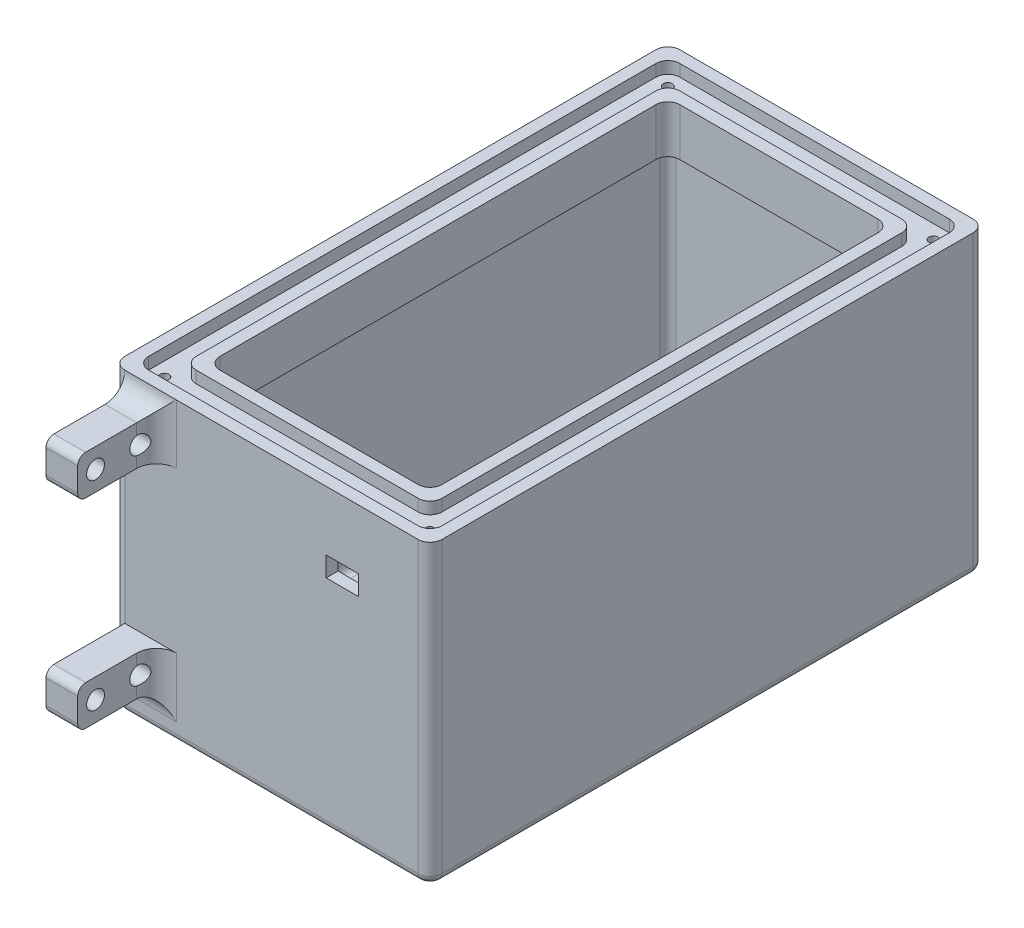
SolidWorks part; units mm, degrees
material "ABS"
ref_plane "Front Plane" through (0, 0, 0) normal (0, 0, 1) x (1, 0, 0)
ref_plane "Top Plane" through (0, 0, 0) normal (0, 1, 0) x (1, 0, 0)
ref_plane "Right Plane" through (0, 0, 0) normal (1, 0, 0) x (0, 0, -1)
sketch "Sketch1" plane through (0, 0, 0) normal (0, 1, 0) x (1, 0, 0)
  line L1 (0, 0) -> (80, 0)
  line L2 (0, 0) -> (0, 140)
  line L3 (0, 140) -> (80, 140)
  line L4 (80, 0) -> (80, 140)
  dimension "D1" = 140
  dimension "D2" = 80
extrude "Boss-Extrude1" add sketch "Sketch1" along normal blind 3
sketch "Sketch2" plane through (0, 3, 0) normal (0, 1, 0) x (1, 0, 0)
  line L1 (0, 140) -> (80, 140)
  line L2 (0, 140) -> (0, 0)
  line L3 (0, 0) -> (80, 0)
  line L4 (80, 140) -> (80, 0)
  line L5 (3, 137) -> (77, 137)
  line L6 (3, 137) -> (3, 3)
  line L7 (3, 3) -> (77, 3)
  line L8 (77, 137) -> (77, 3)
  dimension "D1" = 3
  dimension "D2" = 3
  dimension "D3" = 3
  dimension "D4" = 3
extrude "Boss-Extrude2" add sketch "Sketch2" along normal blind 60
fillet "Fillet1" radius 2 8 edges at (40, 3, -3) (77, 3, -70) (3, 3, -70) (40, 3, -137) (77, 33, -3) (3, 33, -3) (77, 33, -137) (3, 33, -137)
fillet "Fillet2" radius 2 4 edges at (40, 0, -140) (0, 0, -70) (40, 0, 0) (80, 0, -70)
sketch "Sketch6" plane through (0, 63, 0) normal (0, 1, 0) x (1, 0, 0)
  line L1 (0, 140) -> (80, 140)
  line L2 (0, 140) -> (0, 0)
  line L3 (0, 0) -> (80, 0)
  line L4 (80, 140) -> (80, 0)
  line L5 (15, 128) -> (65, 128)
  line L6 (12, 125) -> (12, 15)
  line L7 (15, 12) -> (65, 12)
  line L8 (68, 125) -> (68, 15)
  arc A0 (65, 12) -> (68, 15) centre (65, 15) ccw
  arc A1 (12, 15) -> (15, 12) centre (15, 15) ccw
  arc A2 (65, 128) -> (68, 125) centre (65, 125) cw
  arc A3 (15, 128) -> (12, 125) centre (15, 125) ccw
  dimension "D5" = 3
  dimension "D1" = 12
  dimension "D2" = 12
  dimension "D3" = 12
  dimension "D4" = 12
extrude "Boss-Extrude3" add sketch "Sketch6" along normal blind 12
sketch "Sketch7" plane through (0, 75, 0) normal (0, 1, 0) x (1, 0, 0)
  line L0 (80, 140) -> (0, 140) construction
  line L1 (6, 137) -> (74, 137)
  line L2 (3, 134) -> (3, 6)
  line L3 (6, 3) -> (74, 3)
  line L4 (77, 134) -> (77, 6)
  line L5 (80, 0) -> (80, 140) construction
  line L6 (0, 0) -> (80, 0) construction
  line L7 (0, 140) -> (0, 0) construction
  line L13 (12, 131) -> (68, 131)
  line L14 (9, 128) -> (9, 12)
  line L15 (12, 9) -> (68, 9)
  line L16 (71, 128) -> (71, 12)
  arc A0 (3, 6) -> (6, 3) centre (6, 6) ccw
  arc A1 (74, 3) -> (77, 6) centre (74, 6) ccw
  arc A2 (74, 137) -> (77, 134) centre (74, 134) cw
  arc A3 (6, 137) -> (3, 134) centre (6, 134) ccw
  arc A7 (9, 12) -> (12, 9) centre (12, 12) ccw
  arc A8 (68, 9) -> (71, 12) centre (68, 12) ccw
  arc A9 (68, 131) -> (71, 128) centre (68, 128) cw
  arc A10 (12, 131) -> (9, 128) centre (12, 128) ccw
  dimension "D5" = 3
  dimension "D6" = 6
  dimension "D10" = 3
  dimension "D1" = 3
  dimension "D2" = 3
  dimension "D3" = 3
  dimension "D4" = 3
  dimension "D7" = 6
  dimension "D8" = 6
  dimension "D9" = 6
extrude "Cut-Extrude1" cut sketch "Sketch7" against normal blind 3
sketch "Sketch8" plane through (0, 72, 0) normal (0, 1, 0) x (1, 0, 0)
  line L0 (0, 0) -> (80, 0) construction
  line L1 (0, 140) -> (0, 0) construction
  line L2 (80, 0) -> (80, 140) construction
  line L3 (80, 140) -> (0, 140) construction
  circle A0 centre (6.5, 6.5) radius 1.15
  circle A1 centre (73.5, 6.5) radius 1.15
  circle A2 centre (73.5, 133.5) radius 1.15
  circle A3 centre (6.5, 133.5) radius 1.15
  dimension "D1" = 2.3
  dimension "D2" = 2.3
  dimension "D3" = 2.3
  dimension "D4" = 2.3
  dimension "D5" = 6.5
  dimension "D6" = 6.5
  dimension "D7" = 6.5
  dimension "D8" = 6.5
  dimension "D9" = 6.5
  dimension "D10" = 6.5
  dimension "D11" = 6.5
  dimension "D12" = 6.5
extrude "Cut-Extrude2" cut sketch "Sketch8" against normal blind 6
fillet "Fillet3" radius 3 8 edges at (0.5858, 0.5858, -139.4142) (79.4142, 0.5858, -139.4142) (79.4142, 0.5858, -0.5858) (0.5858, 0.5858, -0.5858) (0, 38.5, -140) (80, 38.5, -140) (80, 38.5, 0) (0, 38.5, 0)
sketch "Sketch9" plane through (0, 0, 0) normal (-1, 0, 0) x (0, 0, 1)
  line L0 (-137, 75) -> (-3, 75) construction
  line L1 (-87, 55) -> (-82, 55)
  line L2 (-87, 55) -> (-87, 29)
  line L3 (-87, 29) -> (-82, 29)
  line L4 (-82, 55) -> (-82, 29)
  line L6 (-140, 2) -> (-140, 75) construction
  line L7 (0, 75) -> (0, 2) construction
  dimension "D1" = 26
  dimension "D2" = 5
  dimension "D3" = 20
  dimension "D4" = 53
  dimension "D5" = 82
extrude "Boss-Extrude4" add sketch "Sketch9" along normal blind 15
sketch "Sketch10" plane through (0, 0, -87) normal (0, 0, -1) x (-1, 0, 0)
  line L0 (15, 29) -> (0, 29) construction
  line L1 (15, 55) -> (10, 55)
  line L2 (15, 55) -> (15, 29)
  line L3 (15, 29) -> (10, 29)
  line L4 (10, 55) -> (10, 29)
  dimension "D1" = 5
extrude "Boss-Extrude5" add sketch "Sketch10" along normal blind 53
fillet "Fillet4" radius 3 4 edges at (0, 29, -84.5) (0, 55, -84.5) (0, 42, -87) (0, 42, -82)
fillet "Fillet5" radius 3 4 edges at (-12.5, 29, -140) (-12.5, 55, -140) (-10, 42, -87) (-15, 42, -82)
sketch "Sketch12" plane through (0, 0, 0) normal (0, 0, 1) x (1, 0, 0)
  line L0 (0, 2) -> (0, 75) construction
  line L1 (3, 70) -> (11, 70)
  line L2 (3, 70) -> (3, 60)
  line L3 (3, 60) -> (11, 60)
  line L4 (11, 70) -> (11, 60)
  line L5 (3, 19.67) -> (11, 19.67)
  line L6 (3, 19.67) -> (3, 9.67)
  line L7 (3, 9.67) -> (11, 9.67)
  line L8 (11, 19.67) -> (11, 9.67)
  line L9 (3, 75) -> (77, 75) construction
  dimension "D1" = 8
  dimension "D2" = 10
  dimension "D3" = 8
  dimension "D4" = 10
  dimension "D5" = 40.33
  dimension "D6" = 3
  dimension "D7" = 5
extrude "Boss-Extrude6" add sketch "Sketch12" along normal blind 19.88
fillet "Fillet6" radius 5 4 edges at (7, 9.67, 0) (11, 14.67, 0) (11, 65, 0) (7, 70, 0)
fillet "Fillet7" radius 2 4 edges at (7, 9.67, 19.88) (7, 19.67, 19.88) (7, 60, 19.88) (7, 70, 19.88)
sketch "Sketch13" plane through (3, 0, 0) normal (-1, 0, 0) x (0, 0, 1)
  line L0 (0, 65) -> (19.88, 65) construction
  line L1 (0, 75) -> (0, 60) construction
  line L2 (19.88, 68) -> (19.88, 62) construction
  line L3 (0, 14.67) -> (19.88, 14.67) construction
  line L4 (0, 19.67) -> (0, 4.67) construction
  line L5 (19.88, 17.67) -> (19.88, 11.67) construction
  circle A0 centre (4.5, 65) radius 2.25
  circle A1 centre (15.38, 65) radius 2.25
  circle A2 centre (4.5, 14.67) radius 2.25
  circle A3 centre (15.38, 14.67) radius 2.25
  dimension "D1" = 4.5
  dimension "D2" = 4.5
  dimension "D3" = 4.5
  dimension "D4" = 4.5
  dimension "D5" = 4.5
  dimension "D6" = 4.5
  dimension "D7" = 4.5
  dimension "D8" = 4.5
extrude "Cut-Extrude3" cut sketch "Sketch13" against normal through all
sketch "Sketch14" plane through (0, 0, 0) normal (0, 0, 1) x (1, 0, 0)
  line L0 (16, 75) -> (77, 75) construction
  line L1 (53.8, 60) -> (62, 60)
  line L2 (53.8, 60) -> (53.8, 55)
  line L3 (53.8, 55) -> (62, 55)
  line L4 (62, 60) -> (62, 55)
  line L5 (77, 2) -> (77, 75) construction
  dimension "D1" = 8.2
  dimension "D2" = 5
  dimension "D3" = 15
  dimension "D4" = 15
extrude "Cut-Extrude4" cut sketch "Sketch14" against normal blind 3
sketch "Sketch15" plane through (0, 0, 0) normal (0, -1, 0) x (1, 0, 0)
  line L0 (0, -70) -> (80, -70) construction
  line L1 (0, -137) -> (0, -3) construction
  line L2 (80, -3) -> (80, -137) construction
  line L3 (40, 0) -> (40, -140) construction
  line L4 (3, 0) -> (77, 0) construction
  line L5 (77, -140) -> (3, -140) construction
  line L7 (21.25, -44.75) -> (58.75, -44.75)
  line L8 (19.75, -46.25) -> (19.75, -93.75)
  line L9 (21.25, -95.25) -> (58.75, -95.25)
  line L10 (60.25, -46.25) -> (60.25, -93.75)
  line L11 (19.75, -44.75) -> (60.25, -95.25) construction
  line L12 (19.75, -95.25) -> (60.25, -44.75) construction
  line L13 (19.25, -42.75) -> (60.75, -42.75)
  line L14 (17.75, -44.25) -> (17.75, -95.75)
  line L15 (19.25, -97.25) -> (60.75, -97.25)
  line L16 (62.25, -44.25) -> (62.25, -95.75)
  line L17 (17.75, -42.75) -> (62.25, -97.25) construction
  line L18 (17.75, -97.25) -> (62.25, -42.75) construction
  arc A0 (19.75, -93.75) -> (21.25, -95.25) centre (21.25, -93.75) ccw
  arc A1 (17.75, -95.75) -> (19.25, -97.25) centre (19.25, -95.75) ccw
  arc A2 (58.75, -95.25) -> (60.25, -93.75) centre (58.75, -93.75) ccw
  arc A3 (60.75, -97.25) -> (62.25, -95.75) centre (60.75, -95.75) ccw
  arc A4 (58.75, -44.75) -> (60.25, -46.25) centre (58.75, -46.25) cw
  arc A5 (60.75, -42.75) -> (62.25, -44.25) centre (60.75, -44.25) cw
  arc A6 (21.25, -44.75) -> (19.75, -46.25) centre (21.25, -46.25) ccw
  arc A7 (19.25, -42.75) -> (17.75, -44.25) centre (19.25, -44.25) ccw
  point P12 (40, -70)
  point P17 (40, -70)
  dimension "D5" = 1.5
  dimension "D1" = 40.5
  dimension "D2" = 50.5
  dimension "D3" = 2
  dimension "D4" = 2
extrude "Boss-Extrude7" add sketch "Sketch15" along normal blind 1.35
sketch "Sketch16" plane through (0, 0, 0) normal (0, -1, 0) x (1, 0, 0)
  line L0 (40, -44.75) -> (40, -95.25) construction
  line L1 (58.75, -44.75) -> (21.25, -44.75) construction
  line L2 (21.25, -95.25) -> (58.75, -95.25) construction
  line L4 (37.5, -46.68) -> (42.5, -46.68)
  line L5 (37.5, -46.68) -> (37.5, -49.38)
  line L6 (37.5, -49.38) -> (42.5, -49.38)
  line L7 (42.5, -46.68) -> (42.5, -49.38)
  line L8 (37.5, -46.68) -> (42.5, -49.38) construction
  line L9 (37.5, -49.38) -> (42.5, -46.68) construction
  point P6 (40, -48.03)
  dimension "D1" = 5
  dimension "D2" = 2.7
  dimension "D3" = 1.93
extrude "Cut-Extrude5" cut sketch "Sketch16" against normal blind 3
